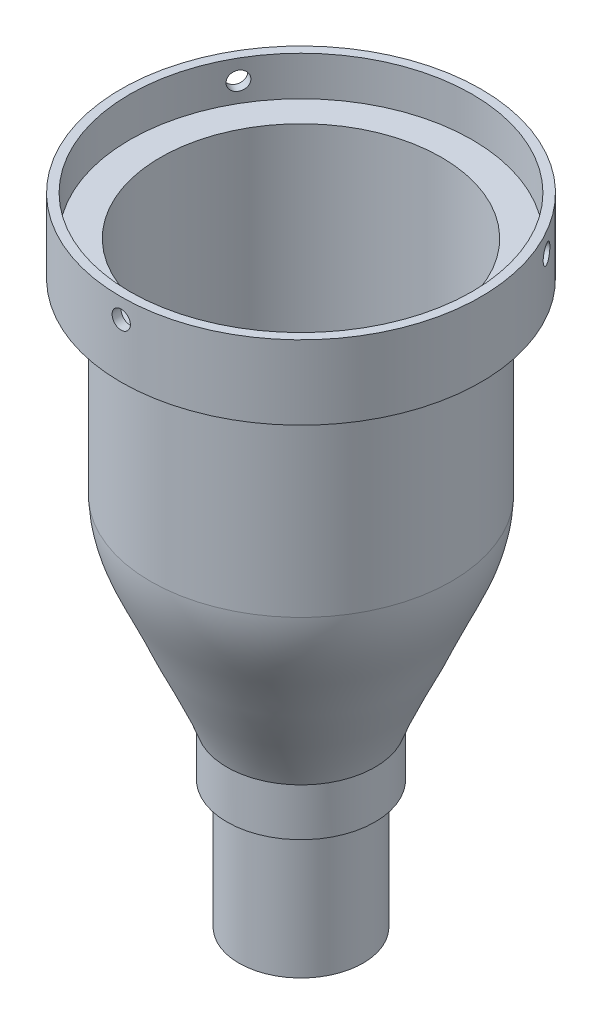
SolidWorks part; units mm, degrees
ref_plane "Płaszczyzna przednia" through (0, 0, 0) normal (0, 0, 1) x (1, 0, 0)
ref_plane "Płaszczyzna górna" through (0, 0, 0) normal (0, 1, 0) x (1, 0, 0)
ref_plane "Płaszczyzna prawa" through (0, 0, 0) normal (1, 0, 0) x (0, 0, -1)
sketch "Sketch1" plane through (0, 0, 0) normal (0, 1, 0) x (1, 0, 0)
  circle A0 centre (0, 0) radius 12.6
  circle A1 centre (0, 0) radius 11.1
  dimension "D1" = 25.2
  dimension "D2" = 1.5
extrude "Boss-Extrude1" add sketch "Sketch1" against normal blind 26
ref_plane "Plane1" through (0, 50, 0) normal (0, 1, 0) x (1, 0, 0)
sketch "Sketch2" plane through (0, 50, 0) normal (0, 1, 0) x (1, 0, 0)
  circle A0 centre (0, 0) radius 28.5
  circle A1 centre (0, 0) radius 30.5
  dimension "D1" = 57
  dimension "D2" = 2
extrude "Boss-Extrude2" add sketch "Sketch2" along normal blind 45 separate body contours A1 | A0
sketch "Sketch6" plane through (0, 0, 0) normal (1, 0, 0) x (0, 0, -1)
  line L1 (-52.0025, 57.5992) -> (47.7591, 57.5992)
  line L2 (-52.0025, 57.5992) -> (-52.0025, -12.321)
  line L3 (-52.0025, -12.321) -> (47.7591, -12.321)
  line L4 (47.7591, 57.5992) -> (47.7591, -12.321)
  line L7 (12.6, 0) -> (11.1, 0)
  line L8 (30.5, 50) -> (28.5, 50)
  line L9 (-28.5, 50) -> (-30.5, 50)
  line L10 (-28.5, 50) -> (-30.5, 50)
  line L11 (30.5, 50) -> (28.5, 50)
  line L12 (0, 0) -> (0, 60.1889) construction
  spline S0 degree 3 poles (12.6, 0) (14.219, 10.4067) (19.2483, 18.8627) (26.0867, 35.4758) (30.1864, 42.333) (30.5, 50) knots 0 0 0 0 0.476692 0.576692 1 1 1 1
  spline S1 degree 3 poles (11.1, 0) (11.5156, 8.4627) (16.3414, 17.4201) (23.8596, 35.0286) (27.0601, 41.7039) (28.5, 50) knots 0 0 0 0 0.530324 0.630324 1 1 1 1
revolve "Revolve2" add sketch "Sketch6" angle 360 about L12 region at (0, 26.2521, -21.1238)
sketch "Sketch7" plane through (0, 95, 0) normal (0, 1, 0) x (1, 0, 0)
  circle A0 centre (0, 0) radius 34.7
  circle A1 centre (0, 0) radius 30.5 construction
  circle A2 centre (0, 0) radius 36.5
  circle A3 centre (0, 0) radius 36.5
  circle M2 centre (0, 0) radius 30.5
  dimension "D2" = 4.2
  dimension "D1" = 6
extrude "Boss-Extrude3" add sketch "Sketch7" against normal blind 7 separate body contours A3 M2 | A3 A0 region at (-33.7185, 95, 0) region at (-35.4676, 95, 0)
sketch "Sketch8" plane through (0, 0, 0) normal (0, 1, 0) x (1, 0, 0)
  circle A0 centre (0, 0) radius 15.0116
  circle A1 centre (0, 0) radius 12.6
extrude "Boss-Extrude4" add sketch "Sketch8" along normal up to surface (9.6199 mm away) contours A0 | A1 up to face at (0, 50, 30.5)
ref_axis "Axis1" through (0, 95, 0) along (0, -1, 0)
extrude "Boss-Extrude5" add sketch "Sketch7<3>" along normal blind 8 contours A0 | A3
sketch "Sketch7<3>" plane through (0, 95, 0) normal (0, 1, 0) x (1, 0, 0) same geometry as "Sketch7"
ref_plane "Plane2" through (0, 0, 36.5) normal (0, 0, 1) x (1, 0, 0)
sketch "Sketch14" plane through (0, 0, 36.5) normal (0, 0, 1) x (1, 0, 0)
  line L0 (0, 103) -> (0, 95) construction
  line L1 (34.7, 103) -> (-34.7, 103) construction
  line L2 (34.7, 95) -> (-34.7, 95) construction
  circle A0 centre (0, 99) radius 1.85
  point P0 (0, 99)
  point P7 (0, 99)
  dimension "D1" = 3.7
extrude "Cut-Extrude1" cut sketch "Sketch14" against normal blind 8 contours A0
pattern_circular "CirPattern1" count 3 over 360 about axis through (0, 103, 0) along (0, 1, 0) of "Cut-Extrude1"
